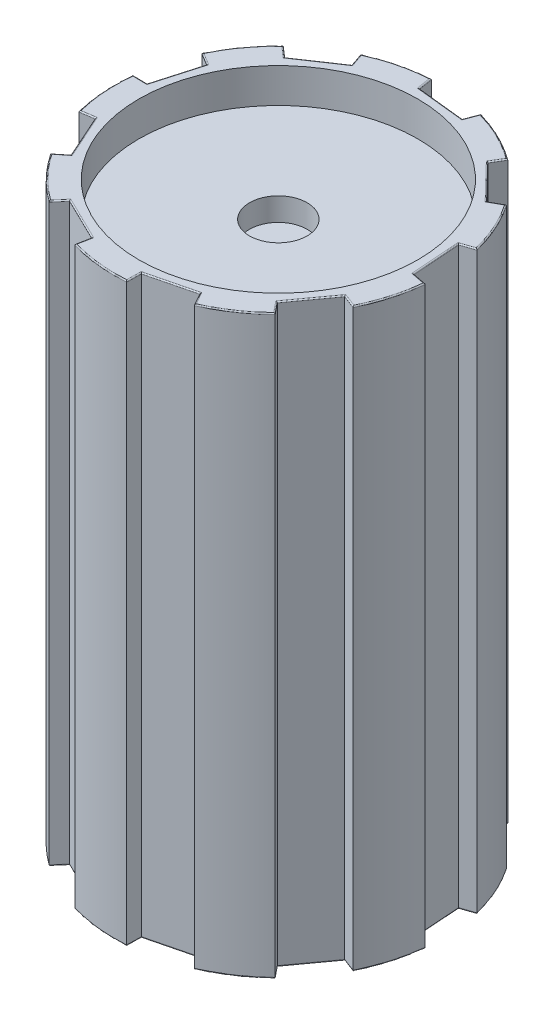
SolidWorks part; units mm, degrees
ref_plane "Front Plane" through (0, 0, 0) normal (0, 0, 1) x (1, 0, 0)
ref_plane "Top Plane" through (0, 0, 0) normal (0, 1, 0) x (1, 0, 0)
ref_plane "Right Plane" through (0, 0, 0) normal (1, 0, 0) x (0, 0, -1)
other "Configuration Table"
sketch "草图1" plane through (0, 0, 0) normal (0, 1, 0) x (1, 0, 0)
  circle A0 centre (0, 0) radius 13
  dimension "D1" = 26
extrude "凸台-拉伸1" add sketch "草图1" along normal blind 50
sketch "草图6" plane through (0, 50, 0) normal (0, 1, 0) x (1, 0, 0)
  circle A0 centre (0, 0) radius 14.25
  dimension "D1" = 28.5
extrude "凸台-拉伸4" add sketch "草图6" against normal through all
sketch "草图2" plane through (0, 50, 0) normal (0, 1, 0) x (1, 0, 0)
  circle A0 centre (0, 0) radius 12
  dimension "D1" = 24
extrude "切除-拉伸1" cut sketch "草图2" against normal blind 3
sketch "草图7" plane through (0, 50, 0) normal (0, 1, 0) x (1, 0, 0)
  line L0 (-16.366, 8.3194) -> (-11.756, 5.5494)
  line L1 (-16.366, 8.3194) -> (-18.2877, 1.6175)
  line L2 (-11.756, 5.5494) -> (-12.9104, 1.5237)
  line L3 (-18.2877, 1.6175) -> (-12.9104, 1.5237)
  line L72 (-7.1895, 16.8929) -> (-5.4386, 11.8077)
  line L73 (-7.1895, 16.8929) -> (-12.9695, 12.9942)
  line L74 (-12.9695, 12.9942) -> (-8.9106, 9.4658)
  line L75 (-5.4386, 11.8077) -> (-8.9106, 9.4658)
  line L76 (5.3511, 17.562) -> (3.4237, 12.5411)
  line L77 (5.3511, 17.562) -> (-1.5827, 18.2908)
  line L78 (-1.5827, 18.2908) -> (-0.7414, 12.9788)
  line L79 (3.4237, 12.5411) -> (-0.7414, 12.9788)
  line L80 (15.3878, 10.0137) -> (10.6839, 7.4063)
  line L81 (15.3878, 10.0137) -> (10.5447, 15.0289)
  line L82 (10.5447, 15.0289) -> (7.7747, 10.4189)
  line L83 (10.6839, 7.4063) -> (7.7747, 10.4189)
  line L84 (18.2244, -2.2201) -> (12.9451, -1.1939)
  line L85 (18.2244, -2.2201) -> (17.7381, 4.7348)
  line L86 (17.7381, 4.7348) -> (12.6529, 2.9838)
  line L87 (12.9451, -1.1939) -> (12.6529, 2.9838)
  line L88 (12.5336, -13.4151) -> (9.149, -9.2355)
  line L89 (12.5336, -13.4151) -> (16.6316, -7.7748)
  line L90 (16.6316, -7.7748) -> (11.6107, -5.8474)
  line L91 (9.149, -9.2355) -> (11.6107, -5.8474)
  line L92 (0.9782, -18.333) -> (1.0721, -12.9557)
  line L93 (0.9782, -18.333) -> (7.743, -16.6464)
  line L94 (7.743, -16.6464) -> (5.1357, -11.9426)
  line L95 (1.0721, -12.9557) -> (5.1357, -11.9426)
  line L96 (-11.0349, -14.6727) -> (-7.5065, -10.6138)
  line L97 (-11.0349, -14.6727) -> (-4.7686, -17.729)
  line L98 (-4.7686, -17.729) -> (-3.7424, -12.4497)
  line L99 (-7.5065, -10.6138) -> (-3.7424, -12.4497)
  line L100 (-17.8847, -4.1469) -> (-12.5727, -3.3055)
  line L101 (-17.8847, -4.1469) -> (-15.0489, -10.516)
  line L102 (-15.0489, -10.516) -> (-10.8693, -7.1315)
  line L103 (-12.5727, -3.3055) -> (-10.8693, -7.1315)
  circle A0 centre (0, 0) radius 13 construction
  point P41 (0, 0)
  point P78 (0, 0)
  point P150 (0, 0)
  dimension "D1" = 26
  dimension "D2" = 105
  dimension "D3" = 105
  dimension "D4" = 9
extrude "切除-拉伸2" cut sketch "草图7" against normal through all
sketch "草图8" plane through (0, 47, 0) normal (0, 1, 0) x (1, 0, 0)
  circle A0 centre (0, 0) radius 2.5
  dimension "D1" = 5
extrude "切除-拉伸3" cut sketch "草图8" against normal blind 2
fillet "圆角6" radius 0.1 36 edges at (-13.5382, 0, -1.5346) (-12.3332, 0, -3.5365) (-12.2942, 0, -5.8728) (-11.5285, 0, -8.376) (-14.2153, 0, 0.994) (12.799, 0, -0.895) (13.2466, 0, -3.1883) (-3.8622, 0, 13.066) (-1.4896, 0, 14.1719) (1.0611, 0, 13.5835) (3.1039, 0, 12.4491) (5.4401, 0, 12.4917) (7.9685, 0, 11.8138) (9.5442, 0, 9.7235) (10.3799, 0, 7.5415) (12.1968, 0, 6.0724) (13.698, 0, 3.9279) (13.5614, 0, 1.3137) (13.018, 0, -5.796) (11.2331, 0, -7.7107) (9.2293, 0, -8.9126) (8.0981, 0, -10.9571) (6.2468, 0, -12.8078) (3.6487, 0, -13.1272) (1.3412, 0, -12.76) (-0.8396, 0, -13.599) (-3.4473, 0, -13.8267) (-5.643, 0, -12.4014) (-7.1746, 0, -10.6368) (-9.3844, 0, -9.8778) (-13.1929, 0, 3.4038) (-11.721, 0, 5.2185) (-11.3573, 0, 7.5266) (-10.2506, 0, 9.8989) (-7.9184, 0, 11.0876) (-5.6244, 0, 11.5317)
fillet "圆角7" radius 0.1 37 edges at (0, 50, 12) (-12.2942, 50, -5.8728) (-12.3332, 50, -3.5365) (-13.5382, 50, -1.5346) (13.2466, 50, -3.1883) (12.799, 50, -0.895) (-14.2153, 50, 0.994) (-11.5285, 50, -8.376) (-10.2506, 50, 9.8989) (-11.3573, 50, 7.5266) (-11.721, 50, 5.2185) (-13.1929, 50, 3.4038) (-9.3844, 50, -9.8778) (-7.1746, 50, -10.6368) (-5.643, 50, -12.4014) (-3.4473, 50, -13.8267) (-0.8396, 50, -13.599) (1.3412, 50, -12.76) (3.6487, 50, -13.1272) (6.2468, 50, -12.8078) (8.0981, 50, -10.9571) (9.2293, 50, -8.9126) (11.2331, 50, -7.7107) (13.018, 50, -5.796) (13.5614, 50, 1.3137) (13.698, 50, 3.9279) (12.1968, 50, 6.0724) (10.3799, 50, 7.5415) (9.5442, 50, 9.7235) (7.9685, 50, 11.8138) (5.4401, 50, 12.4917) (3.1039, 50, 12.4491) (1.0611, 50, 13.5835) (-1.4896, 50, 14.1719) (-3.8622, 50, 13.066) (-5.6244, 50, 11.5317) (-7.9184, 50, 11.0876)
sketch "草图9" plane through (0, 47, 0) normal (0, 1, 0) x (1, 0, 0)
  circle A0 centre (0, 0) radius 12.1
  circle A1 centre (0, 0) radius 12 construction
  dimension "D1" = 0.1
  dimension "D2" = 24.2
extrude "切除-拉伸4" cut sketch "草图9" along normal through all
